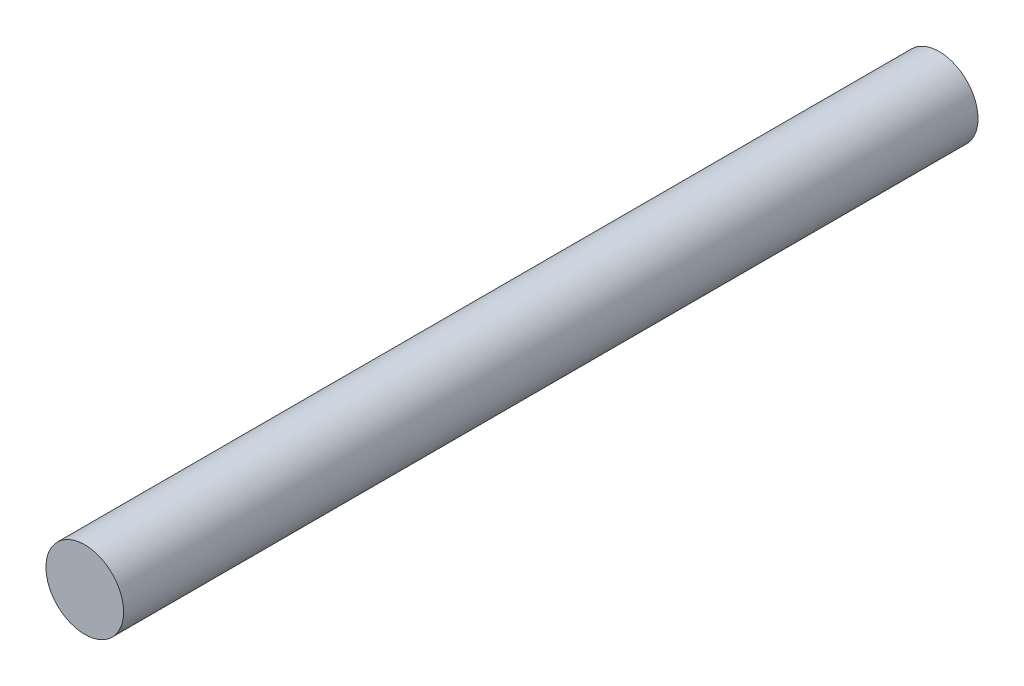
SolidWorks part; units mm, degrees
ref_plane "Front Plane" through (0, 0, 0) normal (0, 0, 1) x (1, 0, 0)
ref_plane "Top Plane" through (0, 0, 0) normal (0, 1, 0) x (1, 0, 0)
ref_plane "Right Plane" through (0, 0, 0) normal (1, 0, 0) x (0, 0, -1)
sketch "Sketch1" plane through (0, 0, 0) normal (0, 0, 1) x (1, 0, 0)
  circle A0 centre (0, 0) radius 4
extrude "Rod" add sketch "Sketch1" along normal blind 88
